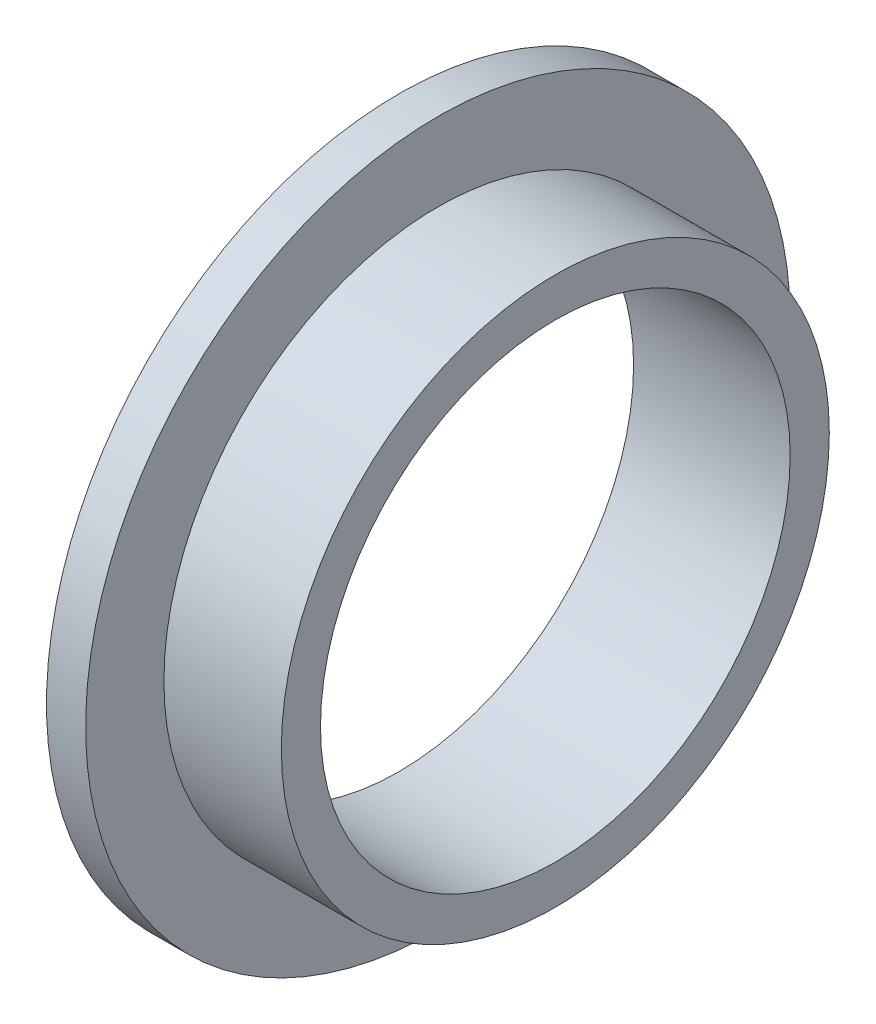
SolidWorks part; units mm, degrees
material "7075-T6 (SN)"
ref_plane "Front Plane" through (0, 0, 0) normal (0, 0, 1) x (1, 0, 0)
ref_plane "Top Plane" through (0, 0, 0) normal (0, 1, 0) x (1, 0, 0)
ref_plane "Right Plane" through (0, 0, 0) normal (1, 0, 0) x (0, 0, -1)
sketch "Sketch1" plane through (0, 0, 0) normal (1, 0, 0) x (0, 0, -1)
  circle A0 centre (0, 0) radius 38.1
  circle A1 centre (0, 0) radius 57.15
  dimension "D1" = 76.2
  dimension "D2" = 114.3
extrude "Boss-Extrude1" add sketch "Sketch1" along normal blind 6.35
sketch "Sketch2" plane through (6.35, 0, 0) normal (1, 0, 0) x (0, 0, -1)
  circle A0 centre (0, 0) radius 44.45
  circle A1 centre (0, 0) radius 38.1
  dimension "D1" = 88.9
  dimension "D2" = 76.2
extrude "Boss-Extrude2" add sketch "Sketch2" along normal blind 19.05
